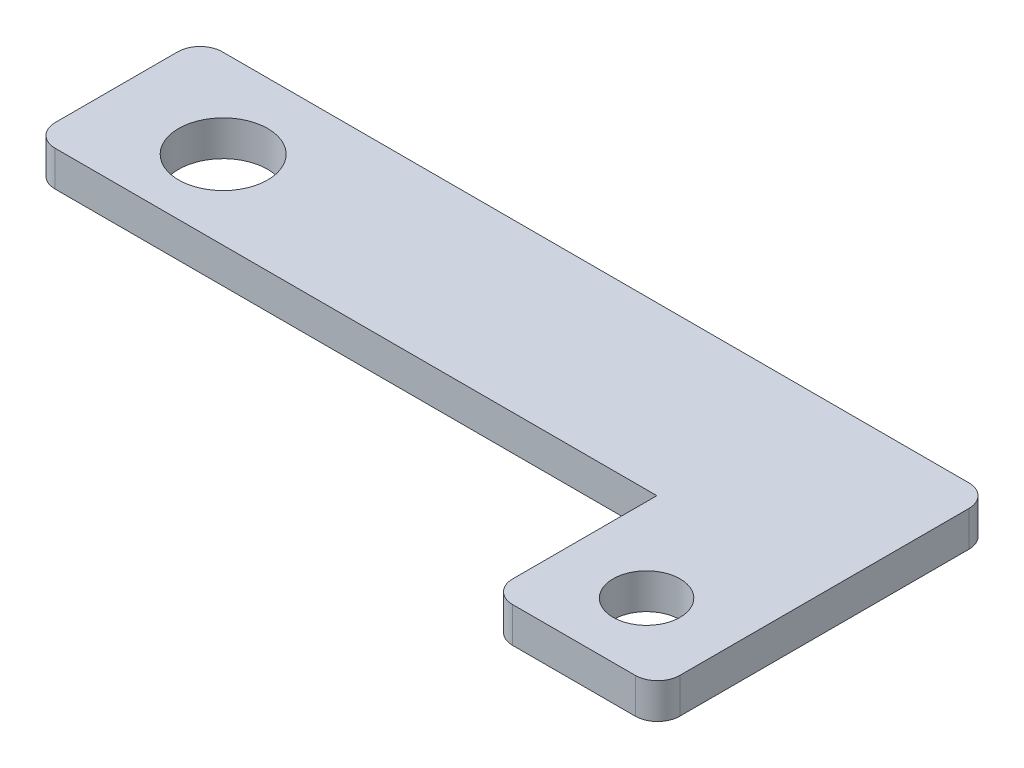
SolidWorks part; units mm, degrees
material "3003-H14"
ref_plane "X-Y Datum" through (0, 0, 0) normal (0, 0, 1) x (1, 0, 0)
ref_plane "X-Z Datum" through (0, 0, 0) normal (0, 1, 0) x (1, 0, 0)
ref_plane "Y-Z Datum" through (0, 0, 0) normal (1, 0, 0) x (0, 0, -1)
sketch "Sketch2" plane through (0, 47.8447, 0) normal (0, -1, 0) x (1, 0, 0)
  line L0 (208.0871, -67.1807) -> (208.0871, -37.2441)
  line L6 (137.0871, -69.2578) -> (137.0871, -46.2578) construction
  line L9 (208.0871, -37.2441) -> (193.0871, -37.2441)
  line L10 (193.0871, -52.1807) -> (193.0871, -37.2441)
  line L12 (137.0871, -67.1807) -> (208.0871, -67.1807)
  line L13 (137.0871, -67.1807) -> (137.0871, -52.1807)
  line L14 (137.0871, -52.1807) -> (193.0871, -52.1807)
  circle A0 centre (147.0871, -59.2578) radius 4 construction
  circle A1 centre (200.5871, -43.7578) radius 3 construction
  circle A2 centre (147.0871, -59.2578) radius 4
  circle A3 centre (200.5871, -43.7578) radius 3
  dimension "D1" = 15
  dimension "D2" = 56
  dimension "D3" = 15
base flange "Base-Flange1" sketch "Sketch2" thickness 3.175 reverse thickness direction yes parameters "D1"=10
fillet "Fillet1" radius 2 5 edges at (208.0871, 46.2572, -67.1807) (208.0871, 46.2572, -37.2441) (137.0871, 46.2572, -52.1807) (193.0871, 46.2572, -37.2441) (137.0871, 46.2572, -67.1807)
sketch "Bend-Lines1" [suppressed] plane through (0, 0, 0) normal (0, 1, 0) x (1, 0, 0)
sketch "Bounding-Box1" [suppressed] plane through (0, 0, 0) normal (0, 1, 0) x (1, 0, 0)
sheet metal parameters "Sheet-Metal1" thickness 3.175 parameters "D1"=10
flat pattern "Flat-Pattern1" [suppressed]
sketch "Bend-Lines2" plane through (0, 0, 0) normal (0, 1, 0) x (1, 0, 0)
sketch3d "Bounding-Box2" [suppressed]
  line L0 (208.0871, 67.1807, 0) -> (137.0871, 67.1807, 0) construction
  line L1 (208.0871, 37.2441, 0) -> (137.0871, 37.2441, 0) construction
  line L2 (208.0871, 67.1807, 0) -> (208.0871, 37.2441, 0) construction
  line L3 (137.0871, 67.1807, 0) -> (137.0871, 37.2441, 0) construction
